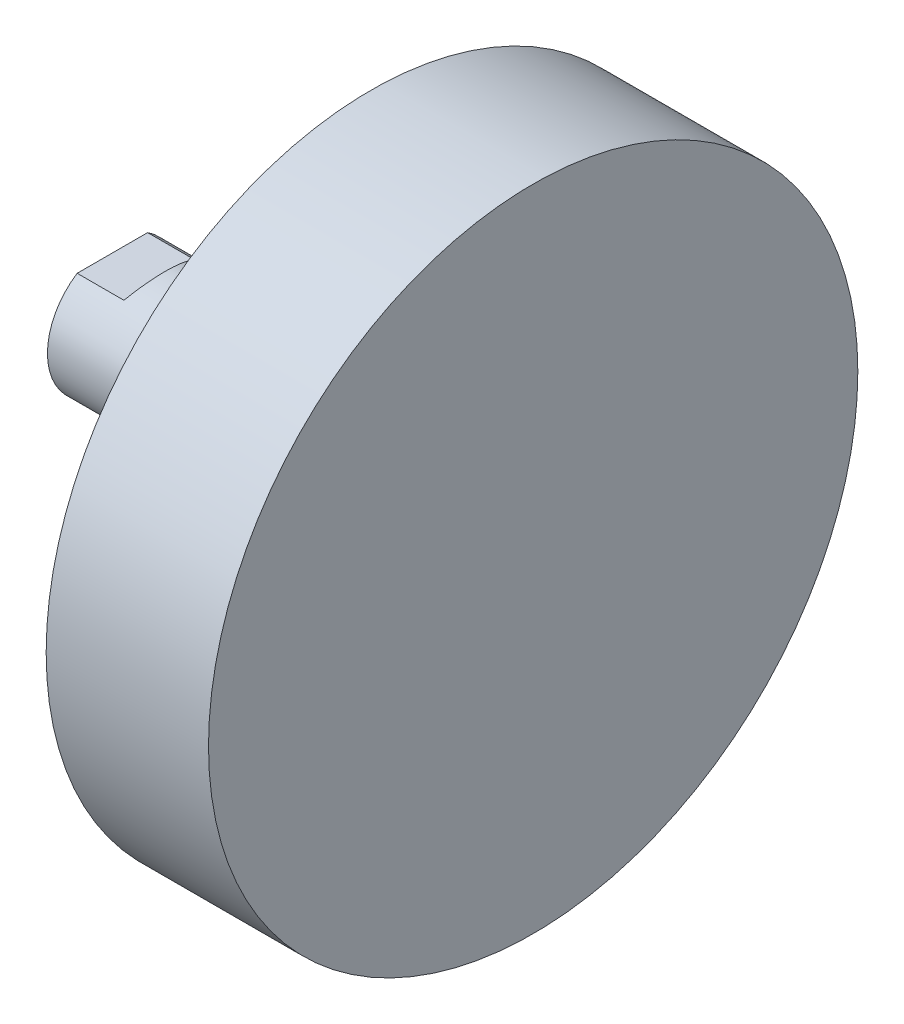
SolidWorks part; units mm, degrees
ref_plane "Front Plane" through (0, 0, 0) normal (0, 0, 1) x (1, 0, 0)
ref_plane "Top Plane" through (0, 0, 0) normal (0, 1, 0) x (1, 0, 0)
ref_plane "Right Plane" through (0, 0, 0) normal (1, 0, 0) x (0, 0, -1)
ref_plane "Plane1" through (0, 0, 0) normal (0, 0, 1) x (1, 0, 0)
sketch "Sketch1" plane through (0, 0, 0) normal (0, 0, 1) x (1, 0, 0)
  line L0 (-11, 0) -> (-11, 12.5)
  line L1 (-11, 12.5) -> (70, 12.5)
  line L2 (70, 12.5) -> (70, 0)
  line L3 (70, 0) -> (-11, 0)
  line L4 (70, 0) -> (-11, 0) construction
revolve "Revolve1" add sketch "Sketch1" angle 360 about L4 reverse direction yes
ref_plane "Plane2" through (0, 0, 0) normal (0, 0, 1) x (1, 0, 0)
sketch "Sketch2" plane through (0, 0, 0) normal (0, 0, 1) x (1, 0, 0)
  line L0 (38.75, 0) -> (38.75, 62.5)
  line L1 (38.75, 62.5) -> (70, 62.5)
  line L2 (70, 62.5) -> (70, 0)
  line L3 (70, 0) -> (38.75, 0)
  line L4 (70, 0) -> (38.75, 0) construction
revolve "Revolve2" add sketch "Sketch2" angle 360 about L4 reverse direction yes
ref_plane "Plane3" through (0, 0, 0) normal (0, 0, 1) x (1, 0, 0)
sketch "Sketch3" plane through (0, 0, 0) normal (0, 0, 1) x (1, 0, 0)
  line L0 (-67, -28) -> (8.1036, -28)
  line L1 (8.1036, -28) -> (-2, -10.5)
  line L2 (-2, -10.5) -> (-11, -10.5)
  line L3 (-11, -10.5) -> (-11, -15.5)
  line L4 (-11, -15.5) -> (-56, -15.5)
  line L5 (-56, -15.5) -> (-56, 15.5)
  line L6 (-56, 15.5) -> (-11, 15.5)
  line L7 (-11, 15.5) -> (-11, 10.5)
  line L8 (-11, 10.5) -> (-2, 10.5)
  line L9 (-2, 10.5) -> (8.1036, 28)
  line L10 (8.1036, 28) -> (-67, 28)
  line L11 (-67, 28) -> (-67, -28)
extrude "Cut-Extrude1" cut sketch "Sketch3" against normal blind 25 and the other way blind 25
ref_plane "Plane4" through (0, 0, 0) normal (0, 0, 1) x (1, 0, 0)
sketch "Sketch4" plane through (0, 0, 0) normal (0, 0, 1) x (1, 0, 0)
  line L0 (-11, 0) -> (-11, 9.5)
  line L1 (-11, 9.5) -> (-10, 8.5)
  line L2 (-10, 8.5) -> (-4, 8.5)
  line L3 (-4, 8.5) -> (-4, 8)
  line L4 (-4, 8) -> (-2.9175, 6.9175)
  line L5 (-2.9175, 6.9175) -> (20.5, 6.9175)
  line L6 (20.5, 6.9175) -> (24.4938, 0)
  line L7 (24.4938, 0) -> (-11, 0)
  line L8 (24.4938, 0) -> (-11, 0) construction
revolve "Cut-Revolve1" cut sketch "Sketch4" angle 360 about L8 reverse direction yes
cosmetic thread "Cosmetic Thread1" parameters "D1"=18, "D2"=16
